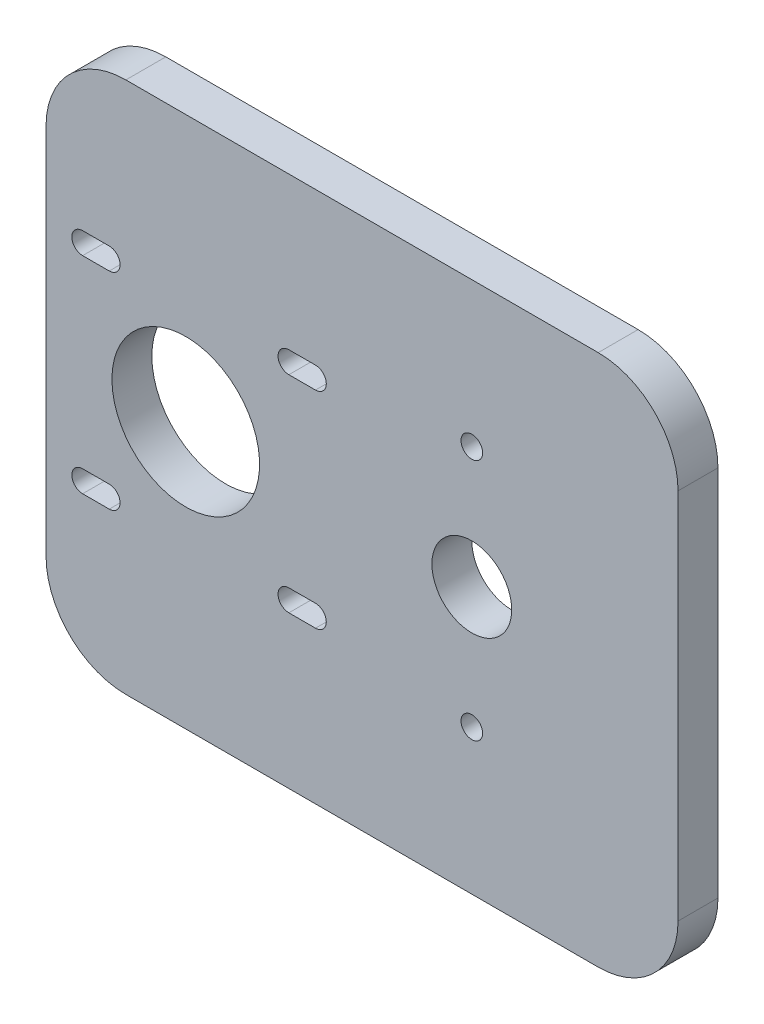
SolidWorks part; units mm, degrees
ref_plane "Alzado" through (0, 0, 0) normal (0, 0, 1) x (1, 0, 0)
ref_plane "Planta" through (0, 0, 0) normal (0, 1, 0) x (1, 0, 0)
ref_plane "Vista lateral" through (0, 0, 0) normal (1, 0, 0) x (0, 0, -1)
sketch "Croquis1" plane through (0, 0, 0) normal (0, 0, 1) x (1, 0, 0)
  line L1 (0, 0) -> (95, 0)
  line L2 (0, 0) -> (0, 80)
  line L3 (0, 80) -> (95, 80)
  line L4 (95, 0) -> (95, 80)
  dimension "D1" = 80
  dimension "D2" = 95
extrude "Saliente-Extruir1" add sketch "Croquis1" along normal blind 6
sketch "Croquis2" plane through (0, 0, 0) normal (0, 0, -1) x (-1, 0, 0)
  line L0 (0, 80) -> (0, 0) construction
  line L1 (-36.5, 55.5) -> (-40.5, 55.5) construction
  line L2 (-36.5, 53.875) -> (-40.5, 53.875)
  line L3 (-36.5, 57.125) -> (-40.5, 57.125)
  line L4 (-36.5, 24.5) -> (-40.5, 24.5) construction
  line L5 (-36.5, 22.875) -> (-40.5, 22.875)
  line L6 (-36.5, 26.125) -> (-40.5, 26.125)
  line L7 (-5.5, 24.5) -> (-9.5, 24.5) construction
  line L8 (-5.5, 22.875) -> (-9.5, 22.875)
  line L9 (-5.5, 26.125) -> (-9.5, 26.125)
  line L10 (-5.5, 55.5) -> (-9.5, 55.5) construction
  line L11 (-5.5, 53.875) -> (-9.5, 53.875)
  line L12 (-5.5, 57.125) -> (-9.5, 57.125)
  circle A3 centre (-21, 40) radius 11.1
  circle A5 centre (-64, 40) radius 6
  arc A7 (-36.5, 53.875) -> (-36.5, 57.125) centre (-36.5, 55.5) ccw
  arc A8 (-40.5, 57.125) -> (-40.5, 53.875) centre (-40.5, 55.5) ccw
  arc A9 (-36.5, 22.875) -> (-36.5, 26.125) centre (-36.5, 24.5) ccw
  arc A10 (-40.5, 26.125) -> (-40.5, 22.875) centre (-40.5, 24.5) ccw
  arc A11 (-5.5, 22.875) -> (-5.5, 26.125) centre (-5.5, 24.5) ccw
  arc A12 (-9.5, 26.125) -> (-9.5, 22.875) centre (-9.5, 24.5) ccw
  arc A13 (-5.5, 53.875) -> (-5.5, 57.125) centre (-5.5, 55.5) ccw
  arc A14 (-9.5, 57.125) -> (-9.5, 53.875) centre (-9.5, 55.5) ccw
  circle A15 centre (-64, 21.75) radius 1.625
  circle A16 centre (-64, 58.25) radius 1.625
  point P4 (-38.5, 55.5)
  point P17 (-38.5, 24.5)
  point P27 (-7.5, 24.5)
  point P34 (-7.5, 55.5)
  dimension "D1" = 3.25
  dimension "D2" = 4
  dimension "D3" = 3.25
  dimension "D4" = 4
  dimension "D5" = 22.2
  dimension "D6" = 12
  dimension "D13" = 3.25
  dimension "D14" = 3.25
  dimension "D7" = 3.25
  dimension "D8" = 4
  dimension "D9" = 3.25
  dimension "D10" = 4
  dimension "D11" = 64
  dimension "D12" = 40
  dimension "D15" = 18.25
  dimension "D16" = 18.25
extrude "Cortar-Extruir1" cut sketch "Croquis2" against normal through all
fillet "Redondeo1" radius 12 4 edges at (95, 0, 3) (95, 80, 3) (0, 0, 3) (0, 80, 3)
